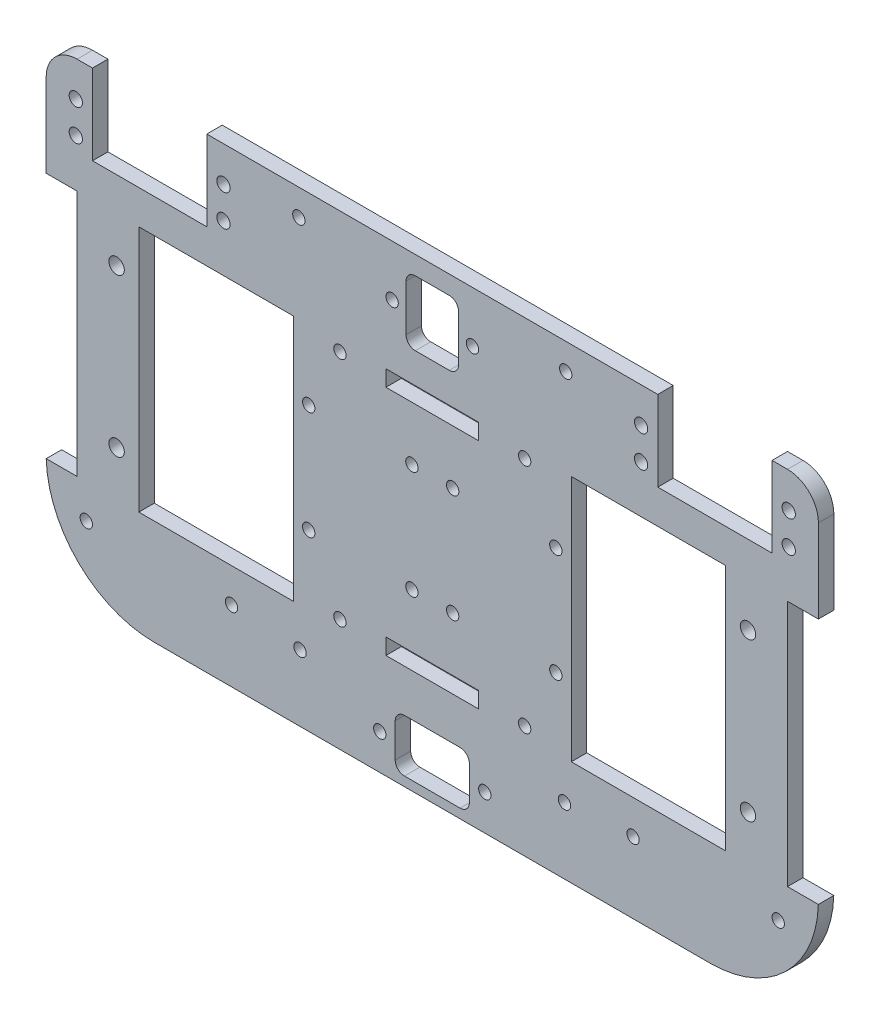
SolidWorks part; units mm, degrees
ref_plane "Front Plane" through (0, 0, 0) normal (0, 0, 1) x (1, 0, 0)
ref_plane "Top Plane" through (0, 0, 0) normal (0, 1, 0) x (1, 0, 0)
ref_plane "Right Plane" through (0, 0, 0) normal (1, 0, 0) x (0, 0, -1)
sketch "Sketch1" plane through (0, 0, 0) normal (0, 0, 1) x (1, 0, 0)
  line L1 (-115, 77) -> (115, 77)
  line L2 (-125, 67) -> (-125, -39)
  line L3 (-90, -74) -> (90, -74)
  line L4 (125, 67) -> (125, -39)
  arc A0 (115, 77) -> (125, 67) centre (115, 67) cw
  arc A1 (-125, 67) -> (-115, 77) centre (-115, 67) cw
  arc A2 (125, -39) -> (90, -74) centre (90, -39) cw
  arc A3 (-125, -39) -> (-90, -74) centre (-90, -39) ccw
  point P7 (125, 77)
  point P10 (-125, 77)
  point P15 (-125, -74)
  dimension "D5" = 10
  dimension "D6" = 10
  dimension "D7" = 35
  dimension "D1" = 250
  dimension "D2" = 151
  dimension "D3" = 74
  dimension "D4" = 125
extrude "Boss-Extrude1" add sketch "Sketch1" along normal blind 5
sketch "Sketch2" plane through (0, 0, 0) normal (0, 0, -1) x (-1, 0, 0)
  line L0 (0, 77) -> (0, -74) construction
  line L4 (-115, 77) -> (115, 77) construction
  line L5 (90, -74) -> (-90, -74) construction
  line L10 (-125, 40) -> (-125, -40)
  line L15 (-115, -40) -> (-125, -40)
  line L16 (-115, 40) -> (-115, -40)
  line L17 (-125, 40) -> (-115, 40)
  line L18 (-45, -40) -> (-95, -40)
  line L19 (-95, -40) -> (-95, 40)
  line L20 (-95, 40) -> (-45, 40)
  line L21 (-45, 40) -> (-45, -40)
  line L22 (125, 40) -> (115, 40)
  line L23 (-125, -39) -> (-125, 67) construction
  line L24 (-192.8803, 0) -> (128.2258, 0) construction
  line L25 (115, 40) -> (115, -40)
  line L26 (115, -40) -> (125, -40)
  line L27 (125, 40) -> (125, -40)
  line L28 (45, 40) -> (45, -40)
  line L29 (95, 40) -> (45, 40)
  line L30 (95, -40) -> (95, 40)
  line L31 (45, -40) -> (95, -40)
  circle A4 centre (-6.6, -17.5) radius 2
  circle A5 centre (-6.6, 17.5) radius 2
  circle A6 centre (-40, -17.5) radius 2
  circle A7 centre (-40, 17.5) radius 2
  circle A8 centre (6.6, 17.5) radius 2
  circle A9 centre (6.6, -17.5) radius 2
  circle A10 centre (40, -17.5) radius 2
  circle A11 centre (40, 17.5) radius 2
  point P24 (-95, 0)
  dimension "D14" = 4
  dimension "D15" = 4
  dimension "D16" = 4
  dimension "D17" = 4
  dimension "D18" = 115
  dimension "D19" = 40
  dimension "D2" = 40
  dimension "D3" = 45
  dimension "D4" = 10
  dimension "D5" = 30
  dimension "D6" = 40
  dimension "D7" = 17.5
  dimension "D8" = 40
  dimension "D9" = 40
  dimension "D10" = 40
  dimension "D11" = 33.4
  dimension "D12" = 33.4
  dimension "D13" = 35
extrude "Cut-Extrude1" cut sketch "Sketch2" against normal blind 10
sketch "Sketch4" plane through (0, 0, 0) normal (0, 0, -1) x (-1, 0, 0)
  line L5 (15, 35) -> (15, 40.2)
  line L7 (-15, 35) -> (-15, 40.2)
  line L9 (-15, -40.2) -> (15, -40.2)
  line L14 (0, 0) -> (-74.7246, 0) construction
  line L15 (15, -35) -> (-15, -35)
  line L16 (0, 0) -> (0, 45.381) construction
  line L20 (15, 35) -> (15, 40.2)
  line L21 (-15, -35) -> (-15, -40.2)
  line L22 (15, -35) -> (15, -40.2)
  line L23 (-15, -35) -> (-15, -40.2)
  line L24 (15, -35) -> (15, -40.2)
  line L25 (-15, 35) -> (-15, 40.2)
  line L26 (15, 35) -> (-15, 35)
  line L27 (-15, 40.2) -> (15, 40.2)
  line L28 (-45, -40) -> (-45, 40) construction
  dimension "D1" = 30
  dimension "D2" = 35
  dimension "D3" = 5.2
  dimension "D4" = 30
extrude "Cut-Extrude3" cut sketch "Sketch4" against normal blind 10 contours L22 L15 L21 L9 | L27 L7 L26 L5
sketch "Sketch6" plane through (0, 0, 0) normal (0, 0, -1) x (-1, 0, 0)
  line L0 (0, 0) -> (-136.3879, 0) construction
  line L1 (0, 0) -> (0, 55.1301) construction
  circle A1 centre (-102.2, -25.5) radius 2.5
  circle A3 centre (-102.2, 25.5) radius 2.5
  circle A4 centre (102.2, -25.5) radius 2.5
  circle A5 centre (102.2, 25.5) radius 2.5
  dimension "D1" = 5
  dimension "D2" = 5
  dimension "D3" = 25.5
  dimension "D4" = 102.2
  dimension "D5" = 51
extrude "Cut-Extrude5" cut sketch "Sketch6" against normal blind 10
sketch "Sketch7" plane through (0, 0, 0) normal (0, 0, -1) x (-1, 0, 0)
  line L0 (0, 0) -> (0, -64.9277) construction
  line L1 (0, 0) -> (-69.7221, 0) construction
  circle A0 centre (29.9, 37.5) radius 2
  circle A1 centre (-29.9, -37.5) radius 2
  circle A2 centre (-29.9, 37.5) radius 2
  circle A3 centre (29.9, -37.5) radius 2
  dimension "D3" = 4
  dimension "D5" = 4
  dimension "D1" = 29.9
  dimension "D2" = 37.5
  dimension "D4" = 59.8
extrude "Cut-Extrude6" cut sketch "Sketch7" against normal blind 10 contours A1 | A3 | A2 | A0
sketch "Sketch8" plane through (0, 0, 0) normal (0, 0, -1) x (-1, 0, 0)
  line L0 (0, 0) -> (0, 89.5315) construction
  line L1 (0, 0) -> (69.2283, 0) construction
  line L2 (5.5, 71) -> (-5.5, 71)
  line L3 (-8.5, 68) -> (-8.5, 53)
  line L4 (-5.5, 50) -> (5.5, 50)
  line L5 (8.5, 53) -> (8.5, 68)
  line L6 (-115, 77) -> (115, 77) construction
  arc A0 (-8.5, 68) -> (-5.5, 71) centre (-5.5, 68) cw
  arc A1 (-8.5, 53) -> (-5.5, 50) centre (-5.5, 53) ccw
  arc A2 (5.5, 50) -> (8.5, 53) centre (5.5, 53) ccw
  arc A3 (5.5, 71) -> (8.5, 68) centre (5.5, 68) cw
  dimension "D5" = 3
  dimension "D1" = 6
  dimension "D2" = 8.5
  dimension "D3" = 8.5
  dimension "D4" = 21
extrude "Cut-Extrude7" cut sketch "Sketch8" against normal blind 70
sketch "Sketch10" plane through (0, 0, 0) normal (0, 0, -1) x (-1, 0, 0)
  line L0 (0, 0) -> (59.5887, 0) construction
  line L1 (0, 0) -> (0, 43.3786) construction
  circle A0 centre (13, 60.5) radius 2
  circle A1 centre (-13, 60.5) radius 2
  dimension "D2" = 4
  dimension "D3" = 4
  dimension "D1" = 13
  dimension "D4" = 13
  dimension "D5" = 60.5
extrude "Cut-Extrude8" cut sketch "Sketch10" against normal blind 5
sketch "Sketch11" plane through (0, 0, 0) normal (0, 0, -1) x (-1, 0, 0)
  line L0 (0, 0) -> (0, -54.4243) construction
  line L1 (0, 0) -> (-72.0295, 0) construction
  line L2 (90, -74) -> (-90, -74) construction
  line L3 (-9, -54) -> (9, -54)
  line L4 (-12, -57) -> (-12, -68)
  line L5 (-9, -71) -> (9, -71)
  line L6 (12, -57) -> (12, -68)
  arc A0 (12, -68) -> (9, -71) centre (9, -68) cw
  arc A1 (12, -57) -> (9, -54) centre (9, -57) ccw
  arc A2 (-12, -68) -> (-9, -71) centre (-9, -68) ccw
  arc A3 (-12, -57) -> (-9, -54) centre (-9, -57) cw
  circle A4 centre (-17, -62.5) radius 2
  circle A5 centre (17, -62.5) radius 2
  dimension "D5" = 3
  dimension "D7" = 4
  dimension "D10" = 4
  dimension "D1" = 12
  dimension "D2" = 12
  dimension "D3" = 17
  dimension "D4" = 20
  dimension "D6" = 11.5
  dimension "D8" = 17
  dimension "D9" = 17
extrude "Cut-Extrude9" cut sketch "Sketch11" against normal blind 10
sketch "Sketch16" plane through (0, 0, 0) normal (0, 0, -1) x (-1, 0, 0)
  line L0 (-110, 77) -> (-110, 51)
  line L1 (-115, 77) -> (115, 77) construction
  line L2 (-110, 51) -> (-73, 51)
  line L3 (-73, 51) -> (-73, 77)
  line L5 (0, 0) -> (0, 95.5672) construction
  line L6 (0, 0) -> (-125.0994, 0) construction
  line L7 (-110, 77) -> (-73, 77)
  line L8 (110, 77) -> (73, 77)
  line L9 (73, 51) -> (73, 77)
  line L10 (110, 51) -> (73, 51)
  line L11 (110, 77) -> (110, 51)
  dimension "D1" = 73
  dimension "D3" = 37
  dimension "D4" = 26
extrude "Cut-Extrude10" cut sketch "Sketch16" against normal blind 10
sketch "Sketch17" plane through (0, 0, 0) normal (0, 0, -1) x (-1, 0, 0)
  line L0 (0, 0) -> (-153.5219, 0) construction
  line L1 (0, 0) -> (0, 113.679) construction
  circle A1 centre (67.6, 65.6) radius 2.15
  circle A3 centre (67.6, 55.4) radius 2.15
  circle A5 centre (115.4, 55.4) radius 2.15
  circle A7 centre (115.4, 65.6) radius 2.15
  circle A8 centre (-115.4, 65.6) radius 2.15
  circle A9 centre (-115.4, 55.4) radius 2.15
  circle A10 centre (-67.6, 55.4) radius 2.15
  circle A11 centre (-67.6, 65.6) radius 2.15
  dimension "D1" = 4.3
  dimension "D2" = 4.3
  dimension "D3" = 4.3
  dimension "D4" = 4.3
  dimension "D5" = 65.6
  dimension "D6" = 115.4
  dimension "D7" = 10.2
  dimension "D8" = 47.8
extrude "Cut-Extrude11" cut sketch "Sketch17" against normal blind 10
sketch "Sketch18" plane through (0, 0, 0) normal (0, 0, -1) x (-1, 0, 0)
  line L0 (-73, 77) -> (73, 77) construction
  line L2 (73, 77) -> (73, 51) construction
  line L3 (-73, 51) -> (-73, 77) construction
  circle A0 centre (-43.2, 68.5) radius 2
  circle A2 centre (43.2, 68.5) radius 2
  dimension "D1" = 4
  dimension "D2" = 68.5
  dimension "D3" = 4
  dimension "D4" = 8.5
  dimension "D5" = 29.8
  dimension "D6" = 29.8
extrude "Cut-Extrude12" cut sketch "Sketch18" against normal blind 10
sketch "Sketch19" plane through (0, 0, 0) normal (0, 0, -1) x (-1, 0, 0)
  line L0 (90, -74) -> (-90, -74) construction
  line L1 (0, 0) -> (0, -74) construction
  line L22 (-73, 51) -> (-110, 51)
  line L23 (-73, 77) -> (-73, 51)
  line L24 (73, 77) -> (-73, 77)
  line L25 (73, 51) -> (73, 77)
  line L26 (110, 51) -> (73, 51)
  line L27 (110, 77) -> (110, 51)
  line L28 (115, 77) -> (110, 77)
  line L29 (125, 40) -> (125, 67)
  line L30 (115, 40) -> (125, 40)
  line L31 (115, -40) -> (115, 40)
  line L32 (124.9857, -40) -> (115, -40)
  line L34 (-90, -74) -> (90, -74)
  line L35 (-125, 67) -> (-125, 40)
  line L36 (-115, -40) -> (-124.9857, -40)
  line L37 (-115, 40) -> (-115, -40)
  line L38 (-125, 40) -> (-115, 40)
  line L40 (-110, 77) -> (-115, 77)
  line L41 (-110, 51) -> (-110, 77)
  line L52 (124.9857, -40) -> (115, -40)
  line L54 (-90, -74) -> (90, -74)
  line L55 (-125, 67) -> (-125, 40)
  line L56 (-115, -40) -> (-124.9857, -40)
  arc A4 (125, 67) -> (115, 77) centre (115, 67) ccw
  arc A5 (90, -74) -> (124.9857, -40) centre (90, -39) ccw
  arc A6 (-124.9857, -40) -> (-90, -74) centre (-90, -39) ccw
  arc A7 (-115, 77) -> (-125, 67) centre (-115, 67) ccw
  arc A9 (90, -74) -> (124.9857, -40) centre (90, -39) ccw
  arc A10 (-124.9857, -40) -> (-90, -74) centre (-90, -39) ccw
  spline S0 degree 2 poles (-115, -40) (-63.7221, -74) (0, -74) knots 0 0 0 1 1 1
  spline S1 degree 2 poles (115, -40) (63.7221, -74) (0, -74) knots 0 0 0 1 1 1
  point P5 (0, -74)
  dimension "D1" = 0
extrude "Cut-Extrude14" [suppressed] cut sketch "Sketch19" against normal blind 5
sketch "Sketch24" plane through (0, 0, 0) normal (0, 0, -1) x (-1, 0, 0)
  line L5 (0, 0) -> (-23.4044, 0) construction
  line L12 (0, 0) -> (0, -63.755) construction
  circle A0 centre (-42.8, -52.5) radius 2
  circle A2 centre (42.8, -52.5) radius 2
  dimension "D1" = 4
  dimension "D2" = 42.8
  dimension "D3" = 52.5
extrude "Cut-Extrude17" cut sketch "Sketch24" against normal blind 5
sketch "Sketch26" plane through (0, 0, 0) normal (0, 0, -1) x (-1, 0, 0)
  line L0 (0, 0) -> (0, -87.1196) construction
  line L1 (0, 0) -> (-65, 0) construction
  circle A1 centre (-112, -51) radius 2
  circle A3 centre (-65, -51) radius 2
  circle A4 centre (65, -51) radius 2
  circle A5 centre (112, -51) radius 2
  dimension "D2" = 65
  dimension "D3" = 4
  dimension "D4" = 4
  dimension "D1" = 51
  dimension "D5" = 47
extrude "Cut-Extrude18" cut sketch "Sketch26" against normal blind 10
